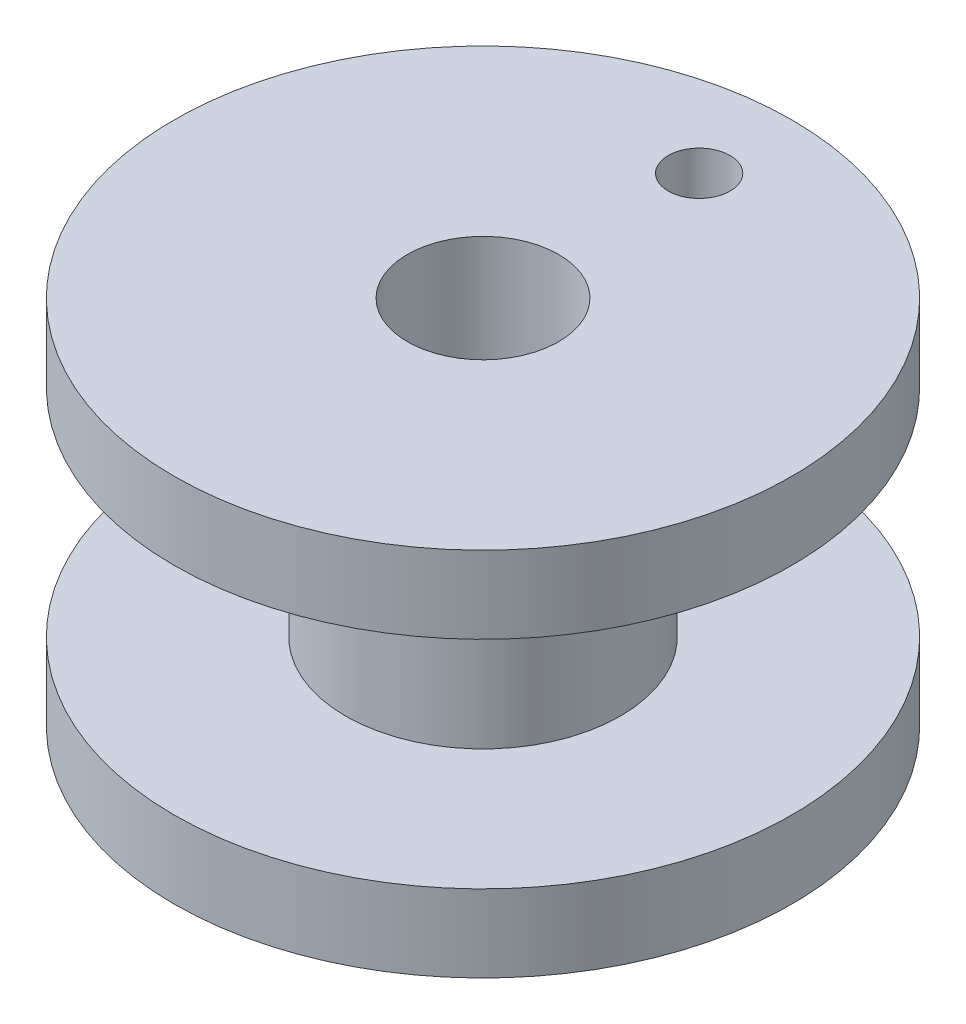
SolidWorks part; units mm, degrees
ref_plane "Front Plane" through (0, 0, 0) normal (0, 0, 1) x (1, 0, 0)
ref_plane "Top Plane" through (0, 0, 0) normal (0, 1, 0) x (1, 0, 0)
ref_plane "Right Plane" through (0, 0, 0) normal (1, 0, 0) x (0, 0, -1)
sketch "Sketch1" plane through (0, 0, 0) normal (0, 1, 0) x (1, 0, 0)
  circle A0 centre (0, 0) radius 12.7
  circle A1 centre (0, 0) radius 3.1115
  circle A2 centre (0, 0) radius 5.6515
  circle A3 centre (0, 8.89) radius 1.27
  dimension "D1" = 25.4
  dimension "D2" = 6.223
  dimension "D3" = 2.54
  dimension "D4" = 2.54
  dimension "D5" = 8.89
extrude "Boss-Extrude1" add sketch "Sketch1" along normal blind 7.62 contours A2 A1 region at (-5.4917, 0, 0)
extrude "Boss-Extrude2" add sketch "Sketch1<4>" along normal blind 3.175 contours A0 A2 region at (-12.3408, 0, 0)
sketch "Sketch1<4>" plane through (0, 0, 0) normal (0, 1, 0) x (1, 0, 0) same geometry as "Sketch1"
mirror "Mirror1" about plane through (0, 7.62, 0) normal (0, 1, 0) of "Boss-Extrude1", "Boss-Extrude2"
